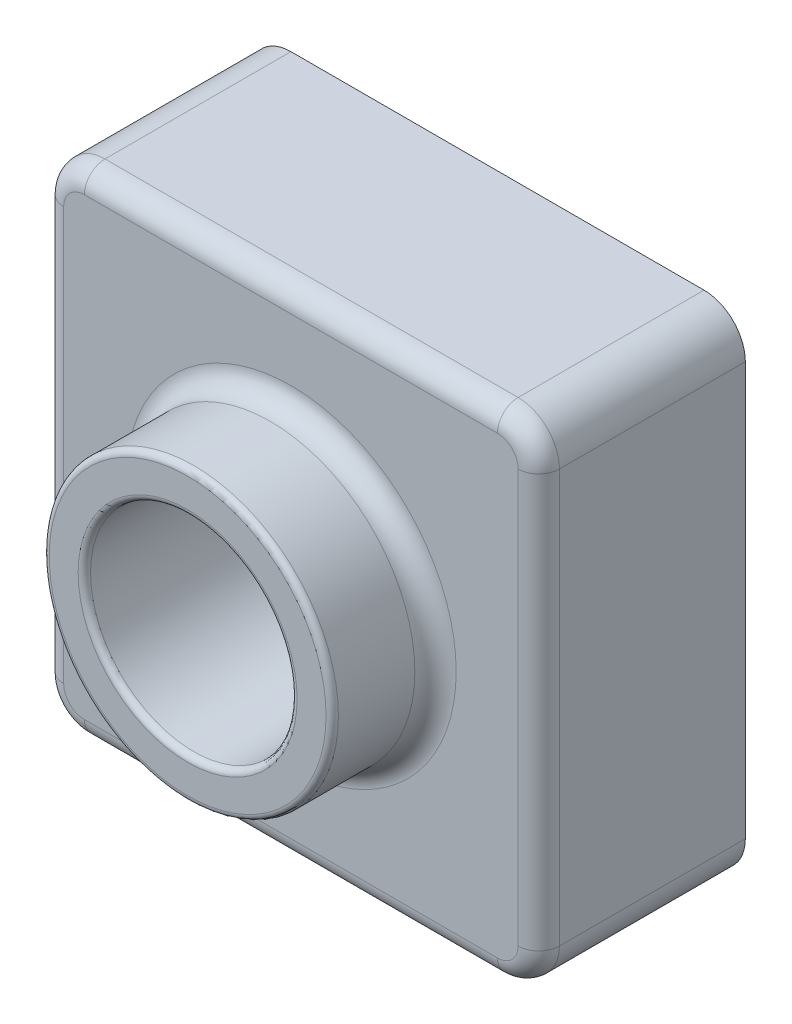
SolidWorks part; units mm, degrees
material "鉻不鏽鋼"
ref_plane "Front" through (0, 0, 0) normal (0, 0, 1) x (1, 0, 0)
ref_plane "Top" through (0, 0, 0) normal (0, 1, 0) x (1, 0, 0)
ref_plane "Right" through (0, 0, 0) normal (1, 0, 0) x (0, 0, -1)
sketch "草圖5" plane through (0, 0, 0) normal (0, 0, 1) x (1, 0, 0)
  line L1 (-60, 60) -> (60, 60)
  line L2 (-60, 60) -> (-60, -60)
  line L3 (-60, -60) -> (60, -60)
  line L4 (60, 60) -> (60, -60)
  line L5 (-60, 60) -> (60, -60) construction
  line L6 (-60, -60) -> (60, 60) construction
  point P0 (0, 0)
  dimension "D1" = 120
  dimension "D2" = 120
extrude "填料-伸長3" add sketch "草圖5" along normal blind 50
sketch "草圖6" plane through (0, 0, 50) normal (0, 0, 1) x (1, 0, 0)
  circle A0 centre (0, 0) radius 35
  dimension "D1" = 70
extrude "填料-伸長4" add sketch "草圖6" along normal blind 25
sketch "草圖7" plane through (0, 0, 75) normal (0, 0, 1) x (1, 0, 0)
  circle A0 centre (0, 0) radius 25
  dimension "D1" = 50
extrude "除料-伸長1" cut sketch "草圖7" against normal through all contours A0
fillet "圓角6" radius 10 4 edges at (60, 60, 25) (60, -60, 25) (-60, -60, 25) (-60, 60, 25)
fillet "圓角1" radius 5 9 edges at (0, -60, 50) (-60, 0, 50) (0, 60, 50) (60, 0, 50) (35, 0, 50) (57.0711, 57.0711, 50) (-57.0711, -57.0711, 50) (-57.0711, 57.0711, 50) (57.0711, -57.0711, 50)
fillet "圓角3" radius 5 1 edges at (25, 0, 0)
fillet "圓角4" radius 1.5 2 edges at (25, 0, 75) (35, 0, 75)
shell "薄殼1" thickness 2 removed face at (30, 0, 0)
